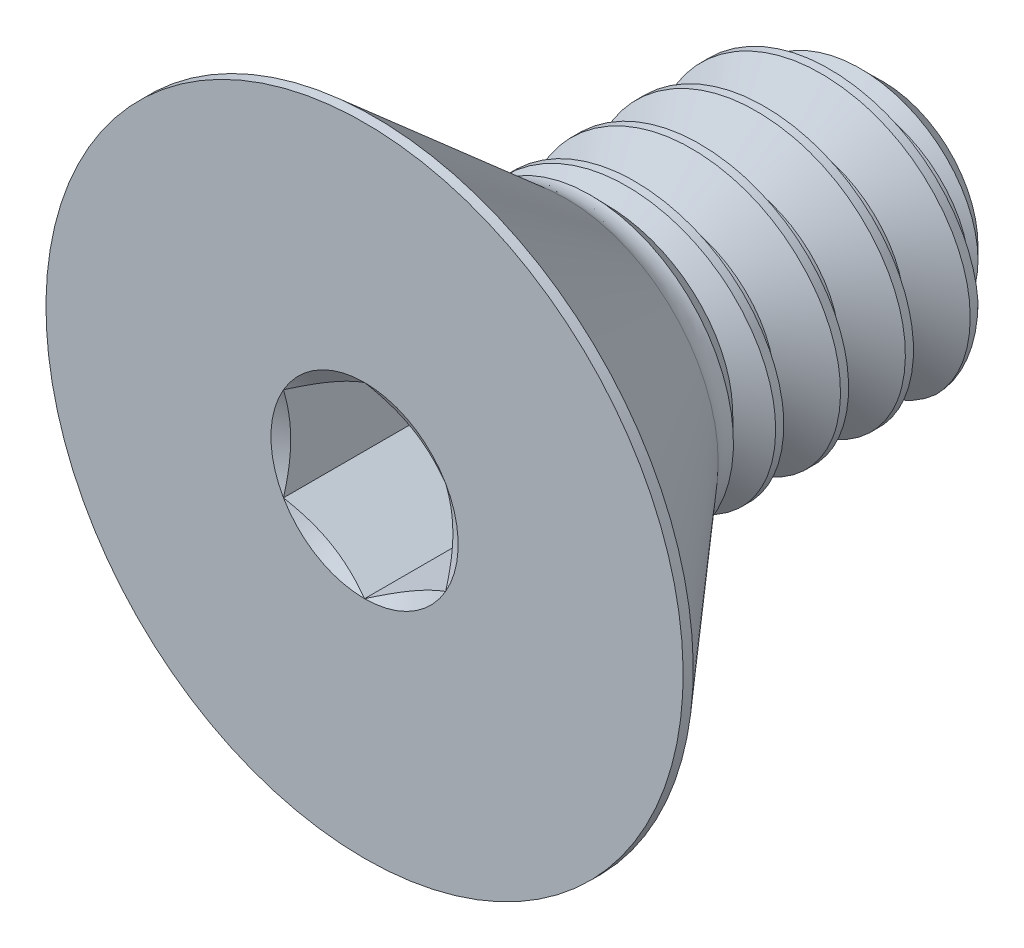
SolidWorks part; units mm, degrees
ref_plane "Front" through (0, 0, 0) normal (0, 0, 1) x (1, 0, 0)
ref_plane "Top" through (0, 0, 0) normal (0, 1, 0) x (1, 0, 0)
ref_plane "Right" through (0, 0, 0) normal (1, 0, 0) x (0, 0, -1)
sketch "Sketch1" plane through (0, 0, 0) normal (1, 0, 0) x (0, 0, -1)
  line L0 (0, 3.8989) -> (0.1232, 3.8989) construction
  line L1 (0.1232, 3.8989) -> (2.4638, 1.8642) construction
  line L2 (0, 1.7526) -> (6.35, 1.7526)
  line L3 (6.35, 1.7526) -> (6.35, 0)
  line L4 (6.35, 0) -> (0, 0)
  line L5 (0, 0) -> (0, 3.8989) construction
  line L6 (0, 3.8989) -> (0, -3.8989) construction
  line L7 (6.35, 1.7526) -> (6.35, -1.7526) construction
  line L8 (0, -3.8989) -> (0.1232, -3.8989) construction
  line L9 (0.1232, -3.8989) -> (2.4638, -1.8642) construction
  line L11 (0, 1.7526) -> (0, 0)
  line L12 (2.7624, 1.7526) -> (2.7624, 0) construction
  line L13 (-19.05, 0) -> (-19.05, 1.7526) construction
  arc A1 (2.4638, 1.8642) -> (2.7624, 1.7526) centre (2.7624, 2.2077) ccw construction
  dimension "D1" = 0.1232
  dimension "Head Ht" = 2.4638
  dimension "Head Dia" = 7.7978
  dimension "Dia" = 3.5052
  dimension "Lg" = 6.35
  dimension "Head Angle" = 82
  dimension "Min Thread" = 25.4
revolve "Revolve1" add sketch "Sketch1" angle 360 mid plane about L4
sketch "Sketch3" plane through (0, 0, -6.35) normal (0, 0, -1) x (-1, 0, 0)
  circle A0 centre (0, 0) radius 1.7526
curve "Helix/Spiral1" pitch 0.7937 height 6.35 radius 1.7526 centre (0, 0, -6.35) axis (0, 0, 1) start towards (0, 1, 0)
sketch "Sketch2" plane through (0, 0, 0) normal (1, 0, 0) x (0, 0, -1)
  line L0 (6.35, 1.7526) -> (7.0445, 1.7526)
  line L1 (7.0445, 1.7526) -> (6.7469, 1.237)
  line L2 (6.7469, 1.237) -> (6.6477, 1.237)
  line L3 (6.6477, 1.237) -> (6.35, 1.7526)
  line L4 (6.4988, 1.4948) -> (6.8957, 1.4948) construction
  dimension "D1" = 60
  dimension "D2" = 0.0992
  dimension "D3" = 0.3969
ref_plane "Plane2" through (0, 0, 19.05) normal (0, 0, 1) x (1, 0, 0)
chamfer "Chamfer1" distance 0.5953 angle 45 1 edges at (0, 1.7526, -6.35)
sweep "Cut-Sweep1" cut profiles "Sketch2" path "Helix/Spiral1"
sketch "Sketch7" plane through (0, 0, 0) normal (1, 0, 0) x (0, 0, -1)
  line L0 (0, 3.8989) -> (0.1232, 3.8989) construction
  line L1 (0.1232, 3.8989) -> (2.4638, 1.8642) construction
  line L2 (0, 3.8989) -> (0.1232, 3.8989)
  line L3 (0.1232, 3.8989) -> (2.4638, 1.8642)
  line L4 (2.7624, 1.7526) -> (2.7624, 0) construction
  line L5 (2.7624, 1.7526) -> (2.7624, 0)
  line L7 (0, 0) -> (0, 3.8989) construction
  line L8 (0, 0) -> (0, 3.8989)
  line L9 (0, 0) -> (2.7624, 0)
  line L10 (5.7417, 0) -> (-5.7417, 0) construction
  arc A0 (2.4638, 1.8642) -> (2.7624, 1.7526) centre (2.7624, 2.2077) ccw construction
  arc A1 (2.4638, 1.8642) -> (2.7624, 1.7526) centre (2.7624, 2.2077) ccw
revolve "Revolve2" add sketch "Sketch7" angle 360 mid plane about L9
ref_plane "Plane1" through (0, 0, -2.7624) normal (0, 0, 1) x (1, 0, 0)
sketch "Sketch8" plane through (0, 0, -2.7624) normal (0, 0, 1) x (1, 0, 0)
  circle A0 centre (0, 0) radius 1.7526
extrude "Boss-Extrude1" add sketch "Sketch8" against normal through all draft 46
sketch "Sketch5" plane through (0, 0, 0) normal (0, 0, 1) x (1, 0, 0)
  line L0 (0, 0) -> (-1.1457, 0) construction
  line L1 (0, 0) -> (-2.7496, 1.5875) construction
  line L2 (0, 0) -> (-2.7496, -1.5875) construction
  line L6 (0, 1.1457) -> (0, 0.9449) construction
  line L7 (0, 0.9449) -> (0, 0.7441) construction
  line L9 (0, 1.1457) -> (-0.9922, 0.5728)
  line L10 (-0.9922, 0.5728) -> (-0.9922, -0.5728)
  line L11 (-0.9922, -0.5728) -> (0, -1.1457)
  line L12 (0, -1.1457) -> (0.9922, -0.5728)
  line L13 (0.9922, -0.5728) -> (0.9922, 0.5728)
  line L14 (0.9922, 0.5728) -> (0, 1.1457)
  circle A0 centre (0, 0) radius 1.1457 construction
  circle A1 centre (0, 0) radius 0.9449 construction
  circle A2 centre (0, 0) radius 0.7441 construction
  circle A3 centre (0, 0) radius 0.9922 construction
  dimension "D3" = 1.4883
  dimension "Hex" = 1.9844
  dimension "D4" = 30
  dimension "D5" = 30
extrude "Cut-Extrude2" cut sketch "Sketch5" against normal blind 1.7247
sketch "Sketch6" plane through (0, 0, 0) normal (0, 0, 1) x (1, 0, 0)
  circle A0 centre (0, 0) radius 1.1457
extrude "Cut-Extrude3" cut sketch "Sketch6" against normal blind 1.7247 draft 60
sketch "Sketch9" [suppressed] plane through (0, 0, -3.6076) normal (0, 0, 1) x (1, 0, 0)
  circle A1 centre (0, 0) radius 2.413
  circle A2 centre (0, 0) radius 2.413
  point P0 (0, 2.413)
  dimension "D1" = 0
extrude "Boss-Extrude2" [suppressed] add sketch "Sketch9" against normal up to surface (15.4424 mm away) up to plane "Plane2"
sketch "Sketch10" plane through (0, 0, 0) normal (1, 0, 0) x (0, 0, -1)
  line L0 (6.35, 1.7526) -> (6.35, -1.7526) construction
  point P0 (5.1594, -1.7526)
  dimension "D1" = 1.1906
equation "\"D3@Helix/Spiral1\" = \"Lg@Sketch1\""
equation "\"D2@Sketch2\" = \"D4@Helix/Spiral1\" * .125"
equation "\"D3@Sketch2\" = \"D4@Helix/Spiral1\" * .5"
equation "\"D1@Chamfer1\" = \"D4@Helix/Spiral1\" * .75"
equation "\"D1@Cut-Extrude2\" = \"Head Ht@Sketch1\" * .7"
equation "\"D1@Sketch1\" = \"Head Ht@Sketch1\" * .05"
equation "\"D1@Sketch10\" = \"D4@Helix/Spiral1\" * 1.5"
equation "\"D1@Cut-Extrude3\" = \"D1@Cut-Extrude2\""
equation "\"D3@Sketch5\" = \"Hex@Sketch5\" * .75"
